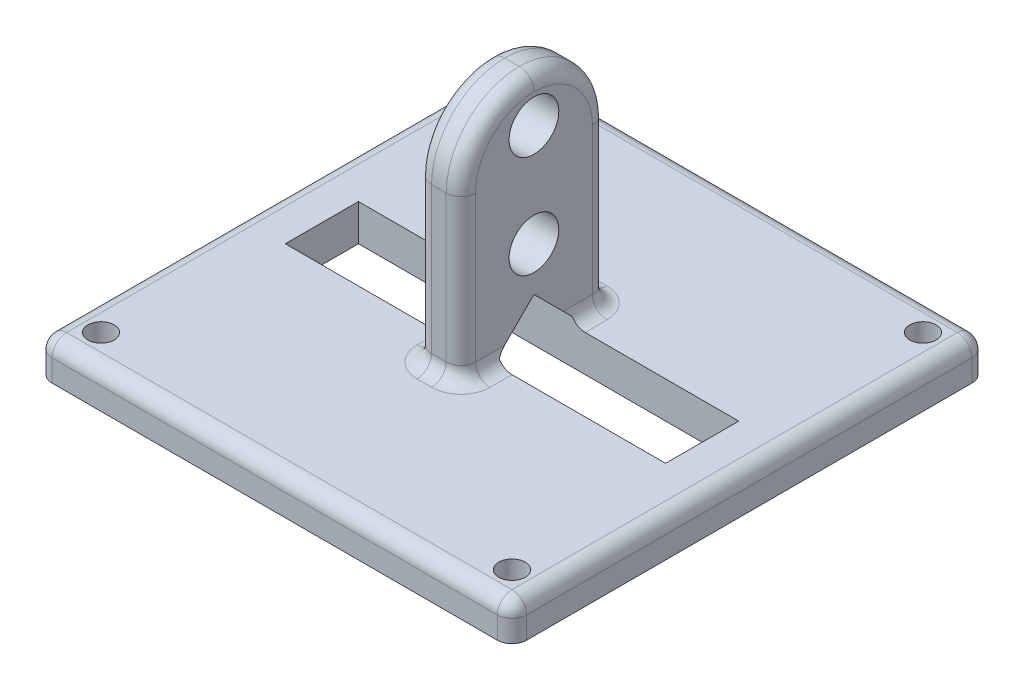
SolidWorks part; units mm, degrees
ref_plane "Front Plane" through (0, 0, 0) normal (0, 0, 1) x (1, 0, 0)
ref_plane "Top Plane" through (0, 0, 0) normal (0, 1, 0) x (1, 0, 0)
ref_plane "Right Plane" through (0, 0, 0) normal (1, 0, 0) x (0, 0, -1)
sketch "Sketch1" plane through (0, 0, 0) normal (0, 1, 0) x (1, 0, 0)
  line L1 (14.05, -14.05) -> (-14.05, -14.05) construction
  line L2 (14.05, -14.05) -> (14.05, 14.05) construction
  line L3 (14.05, 14.05) -> (-14.05, 14.05) construction
  line L4 (-14.05, -14.05) -> (-14.05, 14.05) construction
  line L5 (14.05, -14.05) -> (-14.05, 14.05) construction
  line L6 (14.05, 14.05) -> (-14.05, -14.05) construction
  line L7 (16.225, -16.225) -> (-16.225, -16.225)
  line L8 (16.225, -16.225) -> (16.225, 16.225)
  line L9 (16.225, 16.225) -> (-16.225, 16.225)
  line L10 (-16.225, -16.225) -> (-16.225, 16.225)
  line L11 (16.225, -16.225) -> (-16.225, 16.225) construction
  line L12 (16.225, 16.225) -> (-16.225, -16.225) construction
  line L13 (13, -2.5) -> (-13, -2.5)
  line L14 (13, -2.5) -> (13, 2.5)
  line L15 (13, 2.5) -> (-13, 2.5)
  line L16 (-13, -2.5) -> (-13, 2.5)
  line L17 (13, -2.5) -> (-13, 2.5) construction
  line L18 (13, 2.5) -> (-13, -2.5) construction
  circle A0 centre (-14.05, 14.05) radius 0.9
  circle A1 centre (14.05, 14.05) radius 0.9
  circle A2 centre (14.05, -14.05) radius 0.9
  circle A3 centre (-14.05, -14.05) radius 0.9
  point P0 (0, 0)
  point P10 (0, 0)
  point P15 (0, 0)
  dimension "D1" = 1.8
  dimension "D2" = 28.1
  dimension "D3" = 28.1
  dimension "D4" = 32.45
  dimension "D5" = 32.45
  dimension "D6" = 5
  dimension "D7" = 26
extrude "Boss-Extrude1" add sketch "Sketch1" along normal blind 2.5
sketch "Sketch3" plane through (0, 2.5, 0) normal (0, 1, 0) x (1, 0, 0)
  line L0 (-13, -2.5) -> (13, -2.5) construction
  line L1 (1.5, 2.5) -> (-1.5, 2.5)
  line L2 (1.5, 2.5) -> (1.5, -2.5)
  line L3 (1.5, -2.5) -> (-1.5, -2.5)
  line L4 (-1.5, 2.5) -> (-1.5, -2.5)
  line L5 (1.5, 2.5) -> (-1.5, -2.5) construction
  line L6 (1.5, -2.5) -> (-1.5, 2.5) construction
  line L8 (-1.5, 2.5) -> (1.5, 2.5)
  line L9 (-1.5, 2.5) -> (-1.5, 5)
  line L10 (-1.5, 5) -> (1.5, 5)
  line L11 (1.5, 2.5) -> (1.5, 5)
  line L12 (-1.5, 2.5) -> (1.5, 5) construction
  line L13 (-1.5, 5) -> (1.5, 2.5) construction
  line L14 (1.5, -2.5) -> (-1.5, -2.5)
  line L15 (1.5, -2.5) -> (1.5, -5)
  line L16 (1.5, -5) -> (-1.5, -5)
  line L17 (-1.5, -2.5) -> (-1.5, -5)
  line L18 (1.5, -2.5) -> (-1.5, -5) construction
  line L19 (1.5, -5) -> (-1.5, -2.5) construction
  point P0 (0, 0)
  point P10 (0, 3.75)
  point P13 (0, -3.75)
  line M14 (13, -2.5) -> (-13, -2.5)
  line M16 (-13, 2.5) -> (13, 2.5)
  dimension "D1" = 3
  dimension "D2" = 2.5
extrude "Boss-Extrude2" add sketch "Sketch3" along normal blind 3 contours L17 L16 L15 M14 | L11 L10 L9 M16 region at (0, 2.5, -3.75) region at (0, 2.5, 3.75)
sketch "Sketch4" plane through (0, 5.5, 0) normal (0, 1, 0) x (1, 0, 0)
  line L1 (1.5, -5) -> (-1.5, -5)
  line L2 (1.5, -5) -> (1.5, 5)
  line L3 (1.5, 5) -> (-1.5, 5)
  line L4 (-1.5, -5) -> (-1.5, 5)
  line L5 (1.5, -5) -> (-1.5, 5) construction
  line L6 (1.5, 5) -> (-1.5, -5) construction
  point P4 (0, 0)
extrude "Boss-Extrude3" add sketch "Sketch4" along normal blind 13
chamfer "Chamfer1" distance 2.5 angle 45 2 edges at (0, 5.5, 2.5) (0, 5.5, -2.5)
sketch "Sketch5" plane through (1.5, 0, 0) normal (1, 0, 0) x (0, 0, -1)
  line L0 (0, 18.5) -> (0, 15.5) construction
  line L1 (-5, 18.5) -> (5, 18.5) construction
  line L2 (0, 5.5) -> (0, 8.5) construction
  point P8 (0, 15.5)
  point P9 (0, 8.5)
  dimension "D1" = 3
  dimension "D2" = 7
hole_wizard "M3 Clearance Hole2" positions "Sketch8" profile "Sketch9" hole size "M3" standard "ANSI Metric" end condition up to next
sketch "Sketch8" plane through (1.5, 0, 0) normal (1, 0, 0) x (0, 0, -1)
  point P0 (0, 15.5)
  point P3 (0, 8.5)
sketch "Sketch9" plane through (1.5, 15.5, 0) normal (0, 1, 0) x (0, 0, -1)
  line L0 (0, 0) -> (0, 3)
  line L1 (0, 3) -> (1.7, 3)
  line L2 (1.7, 3) -> (1.7, 0)
  line L5 (1.7, 0) -> (0, 0)
  line L11 (0, -6.35) -> (0, 107.95) construction
  dimension "Thru Hole Dia." = 3.4
  dimension "Thru Hole Depth" = 3
fillet "Fillet1" radius 5 2 edges at (0, 18.5, -5) (0, 18.5, 5)
fillet "Fillet2" radius 1 22 edges at (-1.5, 2.5, -3.75) (1.5, 2.5, -3.75) (0, 2.5, -5) (-1.5, 2.5, 3.75) (0, 2.5, 5) (1.5, 2.5, 3.75) (-1.5, 8, -5) (-1.5, 17.0355, -3.5355) (-1.5, 17.0355, 3.5355) (1.5, 8, -5) (1.5, 17.0355, -3.5355) (1.5, 17.0355, 3.5355) (-1.5, 8, 5) (1.5, 8, 5) (0, 2.5, -16.225) (-16.225, 2.5, 0) (0, 2.5, 16.225) (16.225, 2.5, 0) (-16.225, 1.25, 16.225) (-16.225, 1.25, -16.225) (16.225, 1.25, -16.225) (16.225, 1.25, 16.225)
